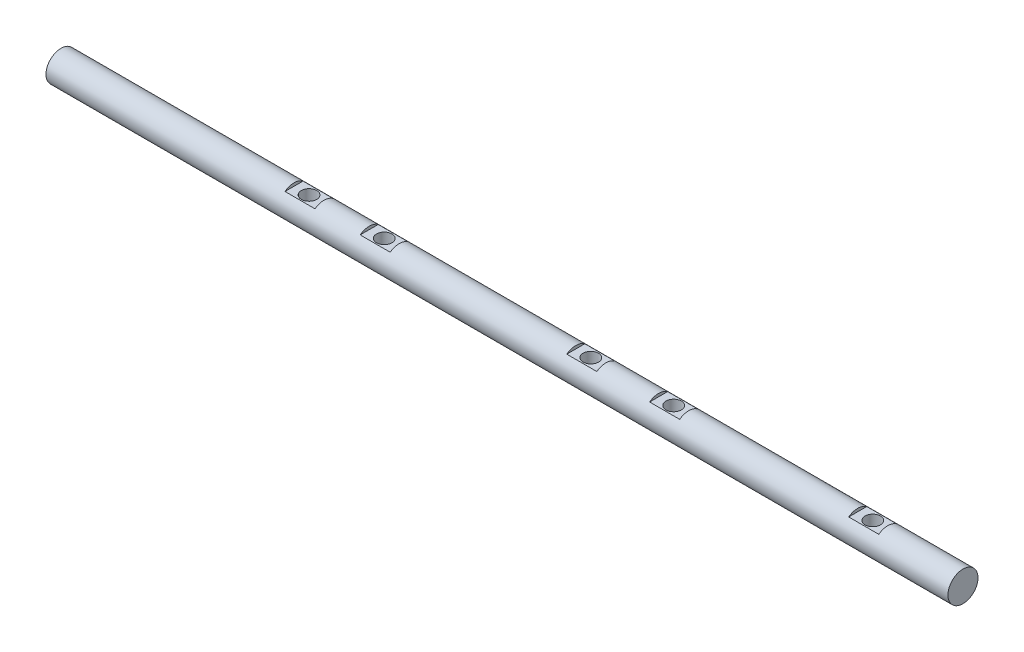
SolidWorks part; units mm, degrees
ref_plane "Front Plane" through (0, 0, 0) normal (0, 0, 1) x (1, 0, 0)
ref_plane "Top Plane" through (0, 0, 0) normal (0, 1, 0) x (1, 0, 0)
ref_plane "Right Plane" through (0, 0, 0) normal (1, 0, 0) x (0, 0, -1)
sketch "Sketch1" plane through (0, 0, 0) normal (1, 0, 0) x (0, 0, -1)
  circle A0 centre (0, 0) radius 3.175
  dimension "D1" = 6.35
extrude "Boss-Extrude1" add sketch "Sketch1" along normal blind 190.5
sketch "Sketch2" plane through (0, 0, 0) normal (0, 1, 0) x (1, 0, 0)
  line L0 (60.325, -3.175) -> (60.325, 3.175)
  line L1 (0, -3.175) -> (190.5, -3.175) construction
  line L2 (190.5, 3.175) -> (0, 3.175) construction
  line L3 (120.65, -3.175) -> (120.65, 3.175)
  line L4 (71.4388, 7.763) -> (65.0888, 7.763)
  line L5 (49.2112, -7.763) -> (55.5612, -7.763)
  line L6 (49.2112, -7.763) -> (49.2112, 7.763)
  line L7 (49.2112, 7.763) -> (55.5612, 7.763)
  line L8 (55.5612, -7.763) -> (55.5612, 7.763)
  line L9 (49.2112, -7.763) -> (55.5612, 7.763) construction
  line L10 (49.2112, 7.763) -> (55.5612, -7.763) construction
  line L11 (108.725, -7.763) -> (115.075, -7.763)
  line L12 (108.725, -7.763) -> (108.725, 7.763)
  line L13 (108.725, 7.763) -> (115.075, 7.763)
  line L14 (115.075, -7.763) -> (115.075, 7.763)
  line L15 (108.725, -7.763) -> (115.075, 7.763) construction
  line L16 (108.725, 7.763) -> (115.075, -7.763) construction
  line L17 (168.275, -10.887) -> (174.625, -10.887)
  line L18 (168.275, -10.887) -> (168.275, 10.887)
  line L19 (168.275, 10.887) -> (174.625, 10.887)
  line L20 (174.625, -10.887) -> (174.625, 10.887)
  line L21 (168.275, -10.887) -> (174.625, 10.887) construction
  line L22 (168.275, 10.887) -> (174.625, -10.887) construction
  line L23 (65.0888, -7.763) -> (65.0888, 7.763)
  line L24 (71.4388, -7.763) -> (65.0888, -7.763)
  line L25 (71.4388, -7.763) -> (71.4388, 7.763)
  line L26 (132.575, 7.763) -> (126.225, 7.763)
  line L27 (126.225, -7.763) -> (126.225, 7.763)
  line L28 (132.575, -7.763) -> (126.225, -7.763)
  line L29 (132.575, -7.763) -> (132.575, 7.763)
  circle A0 centre (171.45, 0) radius 1.632
  circle A1 centre (52.3862, 0) radius 1.6319
  circle A2 centre (111.9, 0) radius 1.632
  circle A3 centre (68.2638, 0) radius 1.6319
  circle A4 centre (129.4, 0) radius 1.632
  dimension "D3" = 3.2639
  dimension "D5" = 6.35
  dimension "D6" = 15.8775
  dimension "D1" = 60.325
  dimension "D2" = 120.65
  dimension "D4" = 171.45
  dimension "D7" = 17.5
extrude "Cut-Extrude1" cut sketch "Sketch2" against normal through all both and the other way through all contours A1 | A3 | A4 | A2 | A0 region at (171.45, 0, 0) region at (52.3862, 0, 0) region at (111.9, 0, 0) region at (68.2638, 0, 0) region at (129.4, 0, 0)
extrude "Cut-Extrude2" cut sketch "Sketch2<3>" along normal through all from offset 2.54 contours L5 L8 L7 L6 A1 | L24 L25 L4 L23 A3 | L28 L29 L26 L27 A4 | L17 L20 L19 L18 A0 | L13 L14 L11 L12 region at (71.271, 0, 0) region at (49.379, 0, 0) region at (168.5018, 0, 0) region at (132.4073, 0, 0)
sketch "Sketch2<3>" plane through (0, 0, 0) normal (0, 1, 0) x (1, 0, 0) same geometry as "Sketch2"
